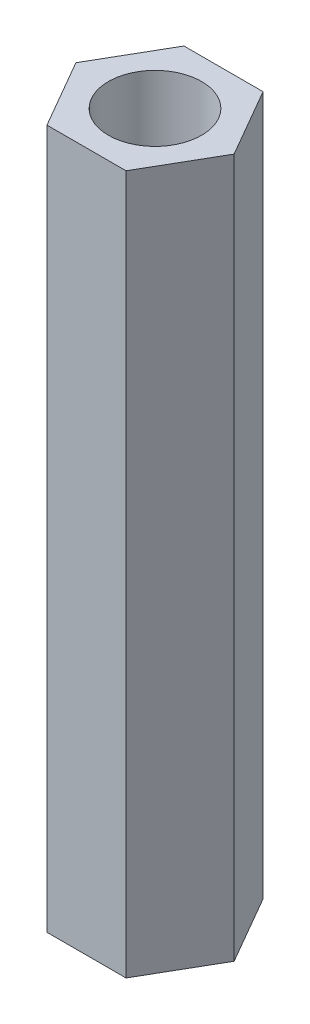
SolidWorks part; units mm, degrees
material "黄铜"
ref_plane "前视基准面" through (0, 0, 0) normal (0, 0, 1) x (1, 0, 0)
ref_plane "上视基准面" through (0, 0, 0) normal (0, 1, 0) x (1, 0, 0)
ref_plane "右视基准面" through (0, 0, 0) normal (1, 0, 0) x (0, 0, -1)
other "Configuration Table"
ref_axis "基准轴1" through (-88.99, 0, 0) along (1, 0, 0)
ref_axis "基准轴2" through (0, 66, 0) along (0, -1, 0)
ref_axis "基准轴3" through (0, 0, -88.99) along (0, 0, 1)
sketch "草图1" plane through (0, 0, 0) normal (0, 1, 0) x (1, 0, 0)
  line L1 (0.8487, 1.47) -> (-0.8487, 1.47)
  line L2 (-0.8487, 1.47) -> (-1.6974, 0)
  line L3 (-1.6974, 0) -> (-0.8487, -1.47)
  line L4 (-0.8487, -1.47) -> (0.8487, -1.47)
  line L5 (0.8487, -1.47) -> (1.6974, 0)
  line L6 (1.6974, 0) -> (0.8487, 1.47)
  circle A0 centre (0, 0) radius 1
  circle A1 centre (0, 0) radius 1.47 construction
  dimension "D1" = 1
  dimension "D2" = 2.94
extrude "凸台-拉伸1" add sketch "草图1" along normal blind 15
